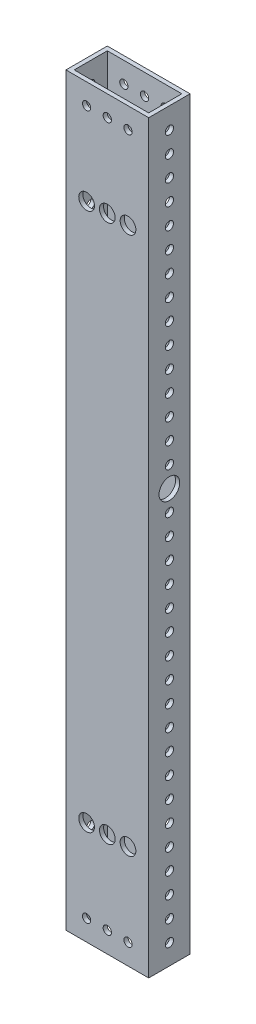
SolidWorks part; units mm, degrees
ref_plane "Front Plane" through (0, 0, 0) normal (0, 0, 1) x (1, 0, 0)
ref_plane "Top Plane" through (0, 0, 0) normal (0, 1, 0) x (1, 0, 0)
ref_plane "Right Plane" through (0, 0, 0) normal (1, 0, 0) x (0, 0, -1)
sketch "Sketch1" plane through (0, 0, 0) normal (0, 1, 0) x (1, 0, 0)
  line L1 (-46.8721, 24.2038) -> (3.9279, 24.2038)
  line L2 (-46.8721, 24.2038) -> (-46.8721, -1.1962)
  line L3 (-46.8721, -1.1962) -> (3.9279, -1.1962)
  line L4 (3.9279, 24.2038) -> (3.9279, -1.1962)
  line L5 (-46.8721, 24.2038) -> (3.9279, -1.1962) construction
  line L6 (-46.8721, -1.1962) -> (3.9279, 24.2038) construction
  line L7 (-44.3321, 21.6638) -> (1.3879, 21.6638)
  line L8 (-44.3321, 21.6638) -> (-44.3321, 1.3438)
  line L9 (-44.3321, 1.3438) -> (1.3879, 1.3438)
  line L10 (1.3879, 21.6638) -> (1.3879, 1.3438)
  line L11 (-44.3321, 21.6638) -> (1.3879, 1.3438) construction
  line L12 (-44.3321, 1.3438) -> (1.3879, 21.6638) construction
  point P0 (-21.4721, 11.5038)
  point P5 (-21.4721, 11.5038)
  dimension "D1" = 2.54
  dimension "D2" = 2.54
  dimension "D3" = 25.4
  dimension "D4" = 50.8
extrude "Boss-Extrude1" add sketch "Sketch1" along normal blind 457.2
sketch "Sketch3" plane through (3.9279, 0, 0) normal (1, 0, 0) x (0, 0, -1)
  line L0 (-1.1962, 457.2) -> (24.2038, 457.2) construction
  line L2 (24.2038, 457.2) -> (24.2038, 0) construction
  circle A0 centre (11.5038, 444.246) radius 2.54
  circle A1 centre (11.5038, 431.546) radius 2.54
  circle A2 centre (11.5038, 418.846) radius 2.54
  circle A3 centre (11.5038, 406.146) radius 2.54
  circle A4 centre (11.5038, 393.446) radius 2.54
  circle A5 centre (11.5038, 380.746) radius 2.54
  circle A6 centre (11.5038, 368.046) radius 2.54
  circle A7 centre (11.5038, 355.346) radius 2.54
  circle A8 centre (11.5038, 342.646) radius 2.54
  circle A9 centre (11.5038, 329.946) radius 2.54
  circle A10 centre (11.5038, 317.246) radius 2.54
  circle A11 centre (11.5038, 304.546) radius 2.54
  circle A12 centre (11.5038, 291.846) radius 2.54
  circle A13 centre (11.5038, 279.146) radius 2.54
  circle A14 centre (11.5038, 266.446) radius 2.54
  circle A16 centre (11.5038, 241.046) radius 2.54
  circle A17 centre (11.5038, 228.346) radius 2.54
  circle A18 centre (11.5038, 215.646) radius 2.54
  circle A19 centre (11.5038, 202.946) radius 2.54
  circle A20 centre (11.5038, 190.246) radius 2.54
  circle A21 centre (11.5038, 177.546) radius 2.54
  circle A22 centre (11.5038, 164.846) radius 2.54
  circle A23 centre (11.5038, 152.146) radius 2.54
  circle A24 centre (11.5038, 139.446) radius 2.54
  circle A25 centre (11.5038, 126.746) radius 2.54
  circle A26 centre (11.5038, 114.046) radius 2.54
  circle A27 centre (11.5038, 101.346) radius 2.54
  circle A28 centre (11.5038, 88.646) radius 2.54
  circle A29 centre (11.5038, 75.946) radius 2.54
  circle A30 centre (11.5038, 63.246) radius 2.54
  circle A31 centre (11.5038, 50.546) radius 2.54
  circle A32 centre (11.5038, 37.846) radius 2.54
  circle A33 centre (11.5038, 25.146) radius 2.54
  circle A34 centre (11.5038, 12.446) radius 2.54
  circle A35 centre (11.5038, 253.746) radius 2.54 [skipped]
  circle A36 centre (11.5038, 253.746) radius 6.35
  dimension "D3" = 5.08
  dimension "D1" = 12.954
  dimension "D2" = 12.7
  dimension "D4" = 35
extrude "Cut-Extrude1" cut sketch "Sketch3" against normal blind 457.2
sketch "Sketch4" plane through (0, 0, -24.2038) normal (0, 0, -1) x (-1, 0, 0)
  line L0 (-3.9279, 457.2) -> (46.8721, 457.2) construction
  line L1 (46.8721, 457.2) -> (46.8721, 0) construction
  line L2 (-3.9279, 457.2) -> (-3.9279, 0) construction
  line L4 (-3.9279, 228.6) -> (46.8721, 228.6) construction
  circle A0 centre (34.1721, 444.5) radius 2.54
  circle A1 centre (21.4721, 444.5) radius 2.54
  circle A2 centre (8.7721, 444.5) radius 2.54
  circle A3 centre (8.7721, 393.7) radius 4.826
  circle A4 centre (21.4721, 393.7) radius 4.826
  circle A5 centre (34.1721, 393.7) radius 4.826
  circle A6 centre (34.1721, 12.7) radius 2.54
  circle A7 centre (21.4721, 12.7) radius 2.54
  circle A8 centre (8.7721, 12.7) radius 2.54
  circle A9 centre (34.1721, 63.5) radius 4.826
  circle A10 centre (21.4721, 63.5) radius 4.826
  circle A11 centre (8.7721, 63.5) radius 4.826
  dimension "D1" = 5.08
  dimension "D6" = 9.652
  dimension "D2" = 12.7
  dimension "D3" = 12.7
  dimension "D5" = 50.8
  dimension "D7" = 12.7
  dimension "D4" = 3
  dimension "D8" = 3
extrude "Cut-Extrude3" cut sketch "Sketch4" against normal blind 457.2
sketch "Sketch5" plane through (0, 0, -24.2038) normal (0, 0, -1) x (-1, 0, 0)
  circle A0 centre (34.4261, 240.7767) radius 2.54
  circle A1 centre (34.4261, 266.1767) radius 2.54
extrude "Cut-Extrude4" cut sketch "Sketch5" against normal blind 2.54
